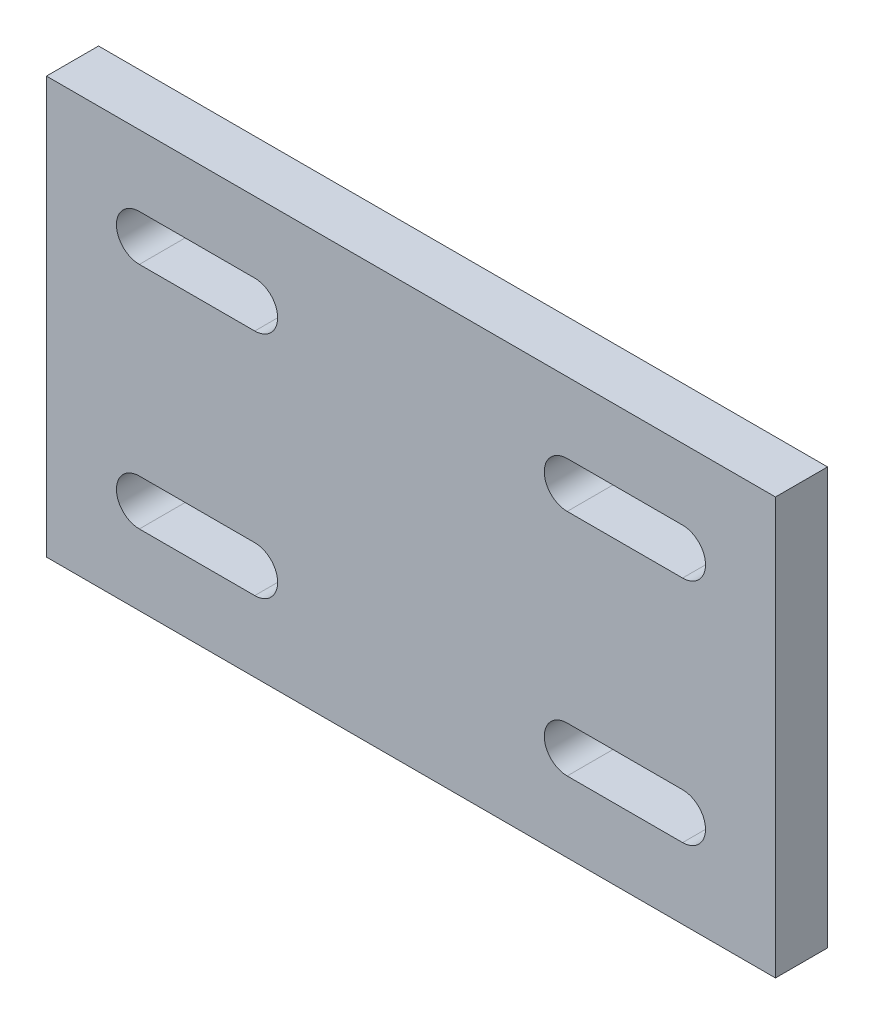
SolidWorks part; units mm, degrees
ref_plane "Front Plane" through (0, 0, 0) normal (0, 0, 1) x (1, 0, 0)
ref_plane "Top Plane" through (0, 0, 0) normal (0, 1, 0) x (1, 0, 0)
ref_plane "Right Plane" through (0, 0, 0) normal (1, 0, 0) x (0, 0, -1)
sketch "Sketch1" plane through (0, 0, 0) normal (0, 0, 1) x (1, 0, 0)
  line L1 (-35, -20) -> (35, -20)
  line L2 (-35, -20) -> (-35, 20)
  line L3 (-35, 20) -> (35, 20)
  line L4 (35, -20) -> (35, 20)
  line L5 (-35, -20) -> (35, 20) construction
  line L6 (-35, 20) -> (35, -20) construction
  point P0 (0, 0)
  dimension "D1" = 70
  dimension "D2" = 40
extrude "Boss-Extrude1" add sketch "Sketch1" along normal blind 5
ref_axis "Axis1" through (0, 55, 5) along (0, -1, 0)
ref_axis "Axis2" through (-88.99, 0, 5) along (1, 0, 0)
sketch "Sketch3" plane through (0, 0, 5) normal (0, 0, 1) x (1, 0, 0)
  line L0 (-26.0809, 11) -> (-15, 11) construction
  line L1 (-26.0809, 13.2) -> (-15, 13.2)
  line L2 (-26.0809, 8.8) -> (-15, 8.8)
  line L7 (-88.99, 0) -> (88.99, 0) construction
  line L8 (0, 55) -> (0, -55) construction
  arc A0 (-26.0809, 13.2) -> (-26.0809, 8.8) centre (-26.0809, 11) ccw
  arc A1 (-15, 8.8) -> (-15, 13.2) centre (-15, 11) ccw
  point P2 (-20.5404, 11)
  dimension "D2" = 2.2
  dimension "D3" = 15
  dimension "D1" = 8.8
extrude "Cut-Extrude1" cut sketch "Sketch3" against normal through all
mirror "Mirror2" about plane through (0, 0, 0) normal (1, 0, 0) of "Cut-Extrude1"
mirror "Mirror3" about plane through (0, 0, 0) normal (0, 1, 0) of "Mirror2"
